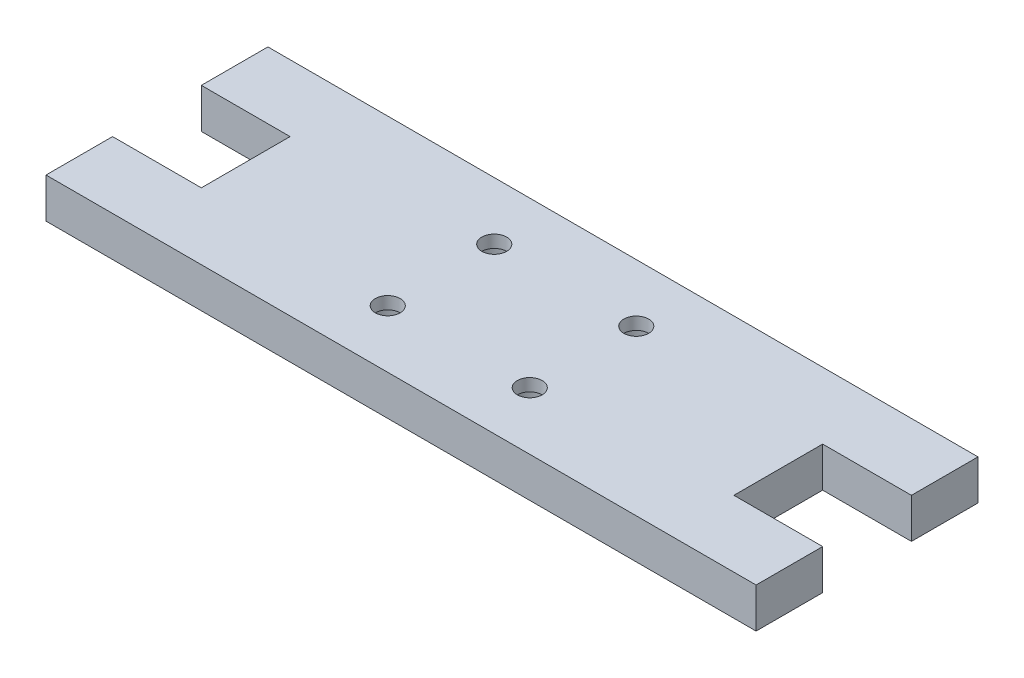
SolidWorks part; units mm, degrees
ref_plane "Front Plane" through (0, 0, 0) normal (0, 0, 1) x (1, 0, 0)
ref_plane "Top Plane" through (0, 0, 0) normal (0, 1, 0) x (1, 0, 0)
ref_plane "Right Plane" through (0, 0, 0) normal (1, 0, 0) x (0, 0, -1)
sketch "Sketch1" plane through (0, 0, 0) normal (1, 0, 0) x (0, 0, -1)
  line L1 (-12.5, -2.25) -> (12.5, -2.25)
  line L2 (-12.5, -2.25) -> (-12.5, 2.25)
  line L3 (-12.5, 2.25) -> (12.5, 2.25)
  line L4 (12.5, -2.25) -> (12.5, 2.25)
  line L5 (-12.5, -2.25) -> (12.5, 2.25) construction
  line L6 (-12.5, 2.25) -> (12.5, -2.25) construction
  point P0 (0, 0)
  dimension "D1" = 4.5
  dimension "D2" = 25
extrude "Boss-Extrude1" add sketch "Sketch1" along normal mid plane 60
sketch "Sketch2" plane through (30, 0, 0) normal (1, 0, 0) x (0, 0, -1)
  line L5 (12.5, 2.25) -> (-12.5, 2.25) construction
  line L6 (-12.5, 2.25) -> (-5, 2.25)
  line L7 (-12.5, 2.25) -> (-12.5, -2.25)
  line L8 (-12.5, -2.25) -> (-5, -2.25)
  line L9 (-5, 2.25) -> (-5, -2.25)
  line L10 (5, 2.25) -> (12.5, 2.25)
  line L11 (5, 2.25) -> (5, -2.25)
  line L12 (5, -2.25) -> (12.5, -2.25)
  line L13 (12.5, 2.25) -> (12.5, -2.25)
  line L14 (-12.5, -2.25) -> (12.5, -2.25) construction
  line L15 (-12.5, 2.25) -> (-12.5, -2.25) construction
  line L16 (12.5, -2.25) -> (12.5, 2.25) construction
  dimension "D1" = 7.5
  dimension "D2" = 7.5
extrude "Boss-Extrude2" add sketch "Sketch2" along normal blind 10
mirror "Mirror1" about plane through (0, 0, 0) normal (1, 0, 0) of "Boss-Extrude2"
sketch "Sketch3" plane through (0, -2.25, 0) normal (0, -1, 0) x (1, 0, 0)
  point P0 (8, 6)
  point P1 (8, -6)
  point P2 (-8, -6)
  point P3 (-8, 6)
  dimension "D1" = 16
  dimension "D2" = 16
  dimension "D3" = 12
  dimension "D4" = 12
  dimension "D5" = 6
  dimension "D6" = 8
hole_wizard "CBORE for M3 SBHCS2" positions "Sketch4" profile "Sketch5" counterbore size "M3" standard "ANSI Metric" end condition through all
sketch "Sketch4" plane through (0, -2.25, 0) normal (0, -1, 0) x (-1, 0, 0)
  point P0 (-8, 6)
  point P3 (8, 6)
  point P6 (8, -6)
  point P9 (-8, -6)
sketch "Sketch5" plane through (8, -2.25, -6) normal (1, 0, 0) x (0, 0, -1)
  line L0 (0, 0) -> (0, 4.5)
  line L1 (0, 4.5) -> (1.4, 4.5)
  line L3 (1.4, 4.5) -> (1.4, 3.1)
  line L4 (1.4, 3.1) -> (2.75, 3.1)
  line L5 (2.75, 3.1) -> (2.75, 0)
  line L7 (2.75, 0) -> (0, 0)
  line L11 (0, -6.35) -> (0, 107.95) construction
  dimension "Thru Hole Dia." = 2.8
  dimension "Thru Hole Depth" = 4.5
  dimension "C'Bore Dia." = 5.5
  dimension "C'Bore Depth" = 3.1
